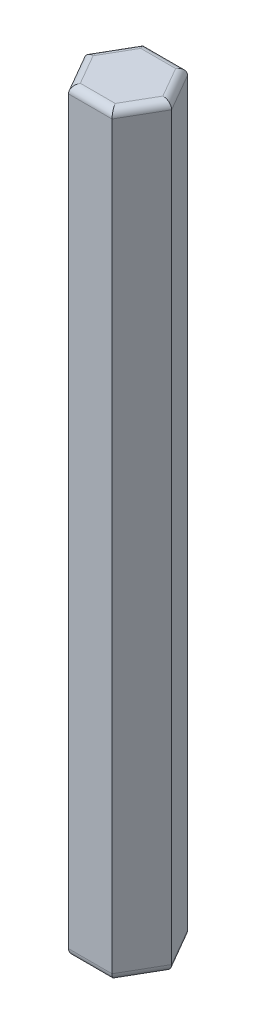
SolidWorks part; units mm, degrees
ref_plane "Plano frontal" through (0, 0, 0) normal (0, 0, 1) x (1, 0, 0)
ref_plane "Plano superior" through (0, 0, 0) normal (0, 1, 0) x (1, 0, 0)
ref_plane "Plano direito" through (0, 0, 0) normal (1, 0, 0) x (0, 0, -1)
ref_plane "Plano1" through (0, -30, 0) normal (0, -1, 0) x (1, 0, 0)
sketch "Esboço1" plane through (0, -30, 0) normal (0, -1, 0) x (1, 0, 0)
  line L0 (-1.4434, -2.5) -> (1.4434, -2.5)
  line L1 (1.4434, -2.5) -> (2.8868, 0)
  line L2 (2.8868, 0) -> (1.4434, 2.5)
  line L3 (1.4434, 2.5) -> (-1.4434, 2.5)
  line L4 (-1.4434, 2.5) -> (-2.8868, 0)
  line L5 (-2.8868, 0) -> (-1.4434, -2.5)
  line L6 (0, 2.5) -> (0, -2.5) construction
  circle A0 centre (0, 0) radius 2.8868 construction
  dimension "D1" = 5
extrude "Ressalto-extrusão1" add sketch "Esboço1" against normal blind 50
fillet "Filete1" radius 0.5 12 edges at (0, -30, 2.5) (2.1651, -30, 1.25) (-2.1651, -30, 1.25) (2.1651, -30, -1.25) (-2.1651, -30, -1.25) (0, -30, -2.5) (0, 20, 2.5) (2.1651, 20, 1.25) (-2.1651, 20, 1.25) (2.1651, 20, -1.25) (-2.1651, 20, -1.25) (0, 20, -2.5)
